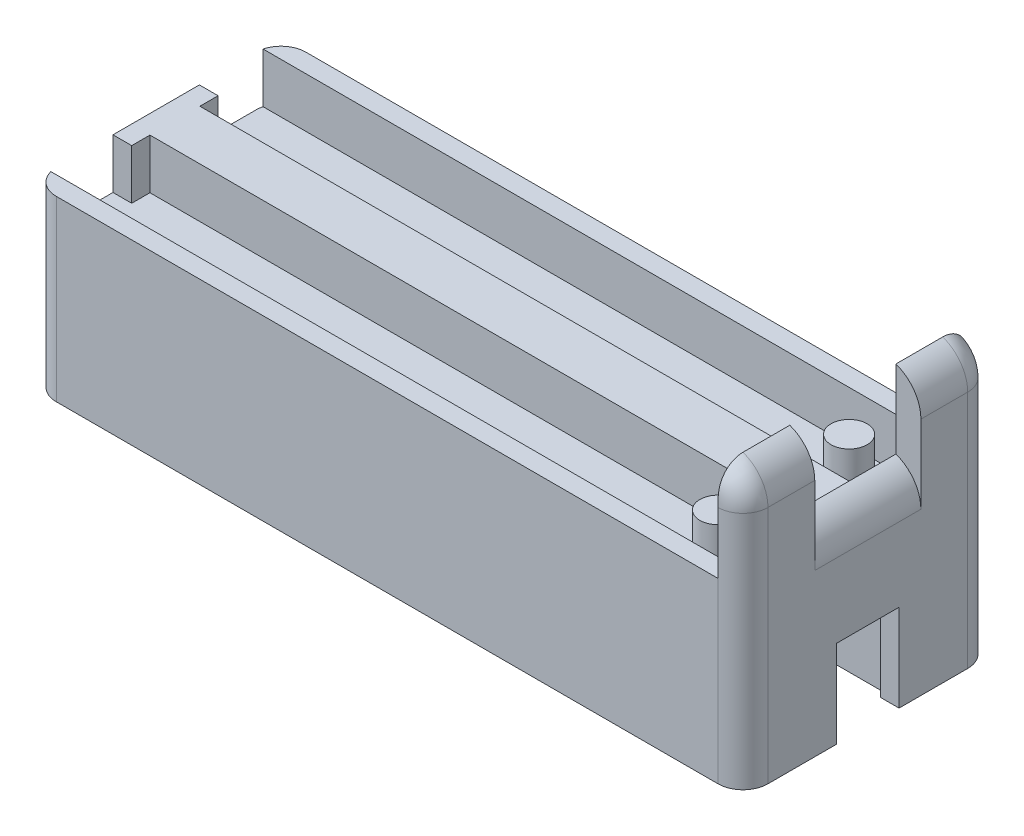
SolidWorks part; units mm, degrees
ref_plane "Front Plane" through (0, 0, 0) normal (0, 0, 1) x (1, 0, 0)
ref_plane "Top Plane" through (0, 0, 0) normal (0, 1, 0) x (1, 0, 0)
ref_plane "Right Plane" through (0, 0, 0) normal (1, 0, 0) x (0, 0, -1)
sketch "Sketch1" plane through (0, 0, 0) normal (0, 1, 0) x (1, 0, 0)
  line L1 (-69.85, -25.4) -> (69.85, -25.4)
  line L2 (-69.85, -25.4) -> (-69.85, 25.4)
  line L3 (-69.85, 25.4) -> (69.85, 25.4)
  line L4 (69.85, -25.4) -> (69.85, 25.4)
  line L5 (-69.85, -25.4) -> (69.85, 25.4) construction
  line L6 (-69.85, 25.4) -> (69.85, -25.4) construction
  point P0 (0, 0)
  dimension "D1" = 139.7
  dimension "D2" = 50.8
extrude "base" add sketch "Sketch1" along normal blind 8.255
sketch "Sketch3" plane through (0, 8.255, 0) normal (0, 1, 0) x (1, 0, 0)
  line L0 (-69.85, 25.4) -> (69.85, 25.4)
  line L1 (69.85, 25.4) -> (69.85, -25.4)
  line L2 (69.85, -25.4) -> (-69.85, -25.4)
  line L3 (-69.85, -25.4) -> (-69.85, -21.59)
  line L4 (-69.85, 25.4) -> (-69.85, -25.4) construction
  line L5 (-69.85, -21.59) -> (66.04, -21.59)
  line L6 (66.04, -21.59) -> (66.04, -5.08)
  line L8 (-69.85, -8.89) -> (-69.85, 8.89)
  line L10 (66.04, 5.08) -> (66.04, 21.59)
  line L11 (66.04, 21.59) -> (-69.85, 21.59)
  line L12 (-69.85, 21.59) -> (-69.85, 25.4)
  line L14 (-69.85, 8.89) -> (-66.04, 8.89)
  line L15 (-66.04, 8.89) -> (-66.04, 5.08)
  line L16 (-66.04, 5.08) -> (66.04, 5.08)
  line L18 (66.04, -5.08) -> (-66.04, -5.08)
  line L19 (-66.04, -5.08) -> (-66.04, -8.89)
  line L20 (-66.04, -8.89) -> (-69.85, -8.89)
  line M14 (69.85, -25.4) -> (69.85, 25.4)
  line M15 (69.85, 25.4) -> (-69.85, 25.4)
  line M16 (-69.85, 25.4) -> (-69.85, -25.4)
  line M17 (-69.85, -25.4) -> (69.85, -25.4)
  dimension "D1" = 3.81
  dimension "D2" = 12.7
  dimension "D3" = 12.7
  dimension "D4" = 3.81
extrude "mechanism walls" add sketch "Sketch3" along normal blind 10.16 contours L20 L19 L18 L6 L5 L11 L10 L16 L15 L14 M16 M17 M14 M15 region at (2.4919, 8.255, 0)
sketch "Sketch4" plane through (0, 8.255, 0) normal (0, 1, 0) x (1, 0, 0)
  line L0 (57.785, 13.335) -> (57.785, -13.335) construction
  line L1 (57.785, 13.335) -> (66.04, 13.335) construction
  line L2 (66.04, 5.08) -> (66.04, 21.59) construction
  line L3 (57.785, -13.335) -> (66.04, -13.335) construction
  line L4 (66.04, -21.59) -> (66.04, -5.08) construction
  line L5 (57.785, 13.335) -> (57.785, 21.59) construction
  line L6 (66.04, 21.59) -> (-69.85, 21.59) construction
  line L7 (57.785, -13.335) -> (57.785, -21.59) construction
  line L8 (-69.85, -21.59) -> (66.04, -21.59) construction
  circle A0 centre (57.785, 13.335) radius 3.683
  circle A1 centre (57.785, -13.335) radius 3.683
  dimension "D1" = 7.366
extrude "spring cylinders" add sketch "Sketch4" along normal up to surface (10.16 mm away) up to face at (-17.4625, 18.415, 0)
sketch "Sketch6" plane through (69.85, 0, 0) normal (1, 0, 0) x (0, 0, -1)
  line L0 (25.4, 18.415) -> (25.4, 0) construction
  line L1 (-25.4, 0) -> (25.4, 0)
  line L2 (-25.4, 0) -> (-25.4, 38.1)
  line L4 (25.4, 0) -> (25.4, 38.1)
  line L5 (-25.4, 38.1) -> (-10.795, 38.1)
  line L6 (-10.795, 38.1) -> (-10.795, 22.225)
  line L7 (-10.795, 22.225) -> (10.795, 22.225)
  line L8 (10.795, 22.225) -> (10.795, 38.1)
  line L9 (10.795, 38.1) -> (25.4, 38.1)
  line L10 (-25.4, 18.415) -> (25.4, 18.415) construction
  dimension "D1" = 3.81
  dimension "D2" = 38.1
  dimension "D3" = 21.59
extrude "wall" add sketch "Sketch6" along normal blind 5.08
sketch "Sketch7" plane through (0, 0, 0) normal (0, -1, 0) x (1, 0, 0)
  line L0 (74.93, 25.4) -> (74.93, 6.35)
  line L1 (-69.85, 25.4) -> (74.93, 25.4)
  line L2 (-69.85, 25.4) -> (-69.85, -25.4)
  line L3 (-69.85, -25.4) -> (74.93, -25.4)
  line L5 (74.93, 25.4) -> (74.93, -25.4) construction
  line L6 (74.93, 6.35) -> (71.12, 6.35)
  line L7 (71.12, 6.35) -> (71.12, 21.59)
  line L8 (71.12, 21.59) -> (-66.04, 21.59)
  line L9 (-66.04, 21.59) -> (-66.04, -21.59)
  line L10 (-66.04, -21.59) -> (71.12, -21.59)
  line L11 (71.12, -21.59) -> (71.12, -6.35)
  line L12 (71.12, -6.35) -> (74.93, -6.35)
  line L13 (74.93, -6.35) -> (74.93, -25.4)
  dimension "D1" = 3.81
  dimension "D4" = 3.81
  dimension "D2" = 3.81
  dimension "D3" = 3.81
  dimension "D5" = 12.7
  dimension "D6" = 15.24
extrude "circuit walls" add sketch "Sketch7" along normal blind 17.78
sketch "Sketch8" plane through (0, 0, 0) normal (0, -1, 0) x (1, 0, 0)
  line L0 (-52.07, 14.605) -> (-66.04, 14.605) construction
  line L1 (-66.04, 21.59) -> (-52.07, 21.59)
  line L2 (-66.04, 21.59) -> (-66.04, 7.62)
  line L3 (-66.04, 7.62) -> (-52.07, 7.62)
  line L4 (-52.07, 21.59) -> (-52.07, 7.62)
  line L5 (-59.055, 21.59) -> (-59.055, 7.62) construction
  line L6 (0, 0) -> (0, 21.59) construction
  line L7 (-66.04, 21.59) -> (71.12, 21.59) construction
  line L8 (0, 0) -> (-66.04, 0) construction
  line L9 (-66.04, -21.59) -> (-66.04, 21.59) construction
  line L10 (-66.04, -21.59) -> (-52.07, -21.59)
  line L11 (-66.04, -21.59) -> (-66.04, -7.62)
  line L12 (-52.07, -21.59) -> (-52.07, -7.62)
  line L13 (-66.04, -7.62) -> (-52.07, -7.62)
  line L14 (2.54, 21.59) -> (2.54, -21.59) construction
  line L15 (71.12, -21.59) -> (-66.04, -21.59) construction
  line L16 (64.135, 21.59) -> (64.135, 7.62) construction
  line L17 (57.15, 14.605) -> (71.12, 14.605) construction
  line L18 (71.12, -7.62) -> (57.15, -7.62)
  line L19 (57.15, -21.59) -> (57.15, -7.62)
  line L20 (71.12, -21.59) -> (71.12, -7.62)
  line L21 (71.12, -21.59) -> (57.15, -21.59)
  line L22 (57.15, 21.59) -> (57.15, 7.62)
  line L23 (71.12, 7.62) -> (57.15, 7.62)
  line L24 (71.12, 21.59) -> (71.12, 7.62)
  line L25 (71.12, 21.59) -> (57.15, 21.59)
  dimension "D2" = 13.97
  dimension "D3" = 2.54
extrude "magnet junctions" add sketch "Sketch8" along normal up to surface (17.78 mm away) up to face at (26.035, -17.78, 0)
sketch "Sketch9" plane through (0, -17.78, 0) normal (0, -1, 0) x (1, 0, 0)
  line L0 (-66.04, 7.62) -> (-66.04, 25.4) construction
  line L1 (74.93, 25.4) -> (-69.85, 25.4) construction
  line L2 (0, 0) -> (-66.04, 0) construction
  line L3 (-52.07, 14.605) -> (-66.04, 14.605) construction
  line L4 (-52.07, 7.62) -> (-52.07, 21.59) construction
  line L5 (-66.04, -7.62) -> (-66.04, 7.62) construction
  line L6 (0, 0) -> (0, 21.59) construction
  line L7 (-52.07, 21.59) -> (57.15, 21.59) construction
  line L8 (2.54, 21.59) -> (2.54, -21.59) construction
  line L9 (-52.07, 21.59) -> (57.15, 21.59) construction
  line L10 (57.15, -21.59) -> (-52.07, -21.59) construction
  circle A0 centre (-59.055, 14.605) radius 4.699
  circle A1 centre (-59.055, -14.605) radius 4.699
  circle A2 centre (64.135, -14.605) radius 4.699
  circle A3 centre (64.135, 14.605) radius 4.699
  point P17 (-59.055, 14.605)
  dimension "D1" = 9.398
  dimension "D3" = 10.795
  dimension "D2" = 2.54
  dimension "D4" = 10.795
extrude "magnet holes" cut sketch "Sketch9" against normal blind 6.096
sketch "Sketch10" plane through (0, 0, 0) normal (0, -1, 0) x (1, 0, 0)
  line L0 (-52.07, 21.59) -> (57.15, 21.59) construction
  line L1 (-52.07, -21.59) -> (-37.07, -21.59)
  line L2 (-52.07, -21.59) -> (-52.07, 21.59)
  line L3 (-52.07, 21.59) -> (-37.07, 21.59)
  line L4 (-37.07, -21.59) -> (-37.07, 21.59)
  line L5 (-52.07, -21.59) -> (-37.07, 21.59) construction
  line L6 (-52.07, 21.59) -> (-37.07, -21.59) construction
  line L8 (-52.07, 7.62) -> (-52.07, 21.59) construction
  line L9 (57.15, -21.59) -> (-52.07, -21.59) construction
  point P0 (-44.57, 0)
  dimension "D1" = 15
extrude "Boss-Extrude1" add sketch "Sketch10" along normal blind 5.334
fillet "Fillet1" radius 7.62 2 edges at (74.93, 38.1, -18.0975) (74.93, 38.1, 18.0975)
fillet "Fillet2" radius 5.08 4 edges at (74.93, 6.5679, -25.4) (74.93, 6.5679, 25.4) (73.5317, 35.3152, -25.4) (73.5317, 35.3152, 25.4)
fillet "Fillet4" radius 7.62 1 edges at (74.93, 22.225, 0)
fillet "Fillet5" radius 5.08 2 edges at (-69.85, 0.3175, -25.4) (-69.85, 0.3175, 25.4)
sketch "Sketch11" plane through (0, 0, 8.89) normal (0, 0, 1) x (1, 0, 0)
  line L1 (-69.85, 18.415) -> (-66.04, 18.415)
  line L2 (-69.85, 18.415) -> (-69.85, 8.255)
  line L3 (-69.85, 8.255) -> (-66.04, 8.255)
  line L4 (-66.04, 18.415) -> (-66.04, 8.255)
extrude "Cut-Extrude1" cut sketch "Sketch11" against normal blind 0.1016
sketch "Sketch12" plane through (0, 0, -8.89) normal (0, 0, -1) x (-1, 0, 0)
  line L1 (66.04, 18.415) -> (71.0041, 18.415)
  line L2 (66.04, 18.415) -> (66.04, 8.255)
  line L3 (66.04, 8.255) -> (71.0041, 8.255)
  line L4 (71.0041, 18.415) -> (71.0041, 8.255)
extrude "Cut-Extrude2" cut sketch "Sketch12" against normal blind 0.1016
equation "\"D3@Sketch3\"=\"D2@Sketch3\""
equation "\"D4@Sketch3\"=\"D1@Sketch3\""
equation "\"D2@Sketch7\"=\"D1@Sketch7\""
equation "\"D3@Sketch7\"=\"D1@Sketch7\""
equation "\"D4@Sketch7\"=\"D1@Sketch7\""
